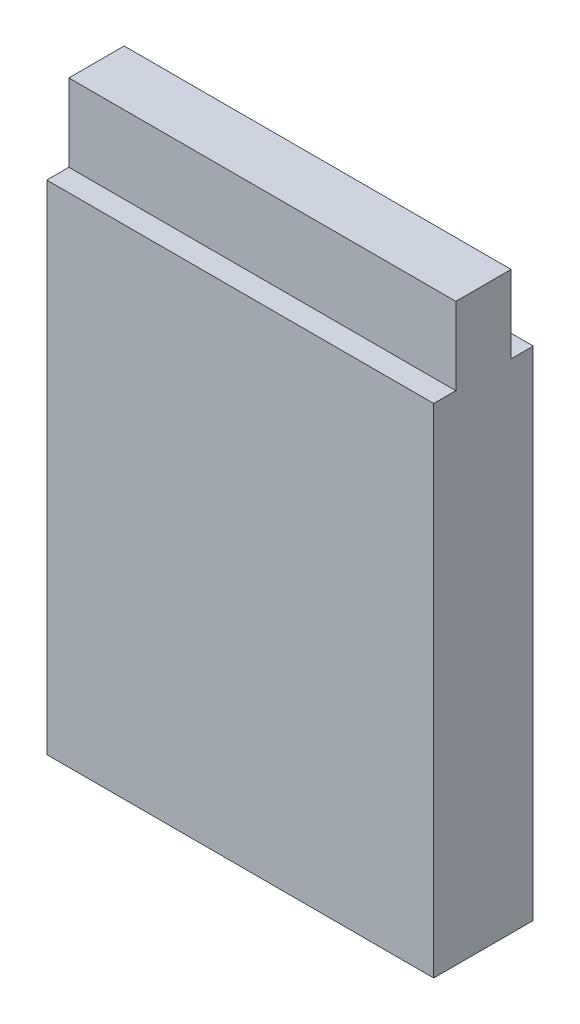
SolidWorks part; units mm, degrees
ref_plane "Front" through (0, 0, 0) normal (0, 0, 1) x (1, 0, 0)
ref_plane "Top" through (0, 0, 0) normal (0, 1, 0) x (1, 0, 0)
ref_plane "Side" through (0, 0, 0) normal (1, 0, 0) x (0, 0, -1)
ref_axis "X_Axis" through (-20.1896, 0, 0) along (1, 0, 0)
ref_axis "Y_Axis" through (0, -14.8261, 0) along (0, 1, 0)
ref_axis "Z_Axis" through (0, 0, -19.842) along (0, 0, 1)
sketch "Sketch1" plane through (0, 0, 0) normal (0, 0, 1) x (1, 0, 0)
  line L1 (17.5, -22.5) -> (-17.5, -22.5)
  line L2 (17.5, -22.5) -> (17.5, 22.5)
  line L3 (17.5, 22.5) -> (-17.5, 22.5)
  line L4 (-17.5, -22.5) -> (-17.5, 22.5)
  line L5 (17.5, -22.5) -> (-17.5, 22.5) construction
  line L6 (17.5, 22.5) -> (-17.5, -22.5) construction
  point P0 (0, 0)
  dimension "D1" = 35
  dimension "D2" = 45
extrude "Boss-Extrude1" add sketch "Sketch1" along normal mid plane 9
sketch "Sketch3" plane through (0, 22.5, 0) normal (0, 1, 0) x (1, 0, 0)
  line L0 (-17.5, -4.5) -> (-17.5, 4.5) construction
  line L1 (17.5, 2.5) -> (-17.5, 2.5)
  line L2 (17.5, 2.5) -> (17.5, -2.5)
  line L3 (17.5, -2.5) -> (-17.5, -2.5)
  line L4 (-17.5, 2.5) -> (-17.5, -2.5)
  line L5 (17.5, 2.5) -> (-17.5, -2.5) construction
  line L6 (17.5, -2.5) -> (-17.5, 2.5) construction
  point P0 (0, 0)
  dimension "D1" = 5
extrude "Boss-Extrude2" add sketch "Sketch3" along normal blind 7
